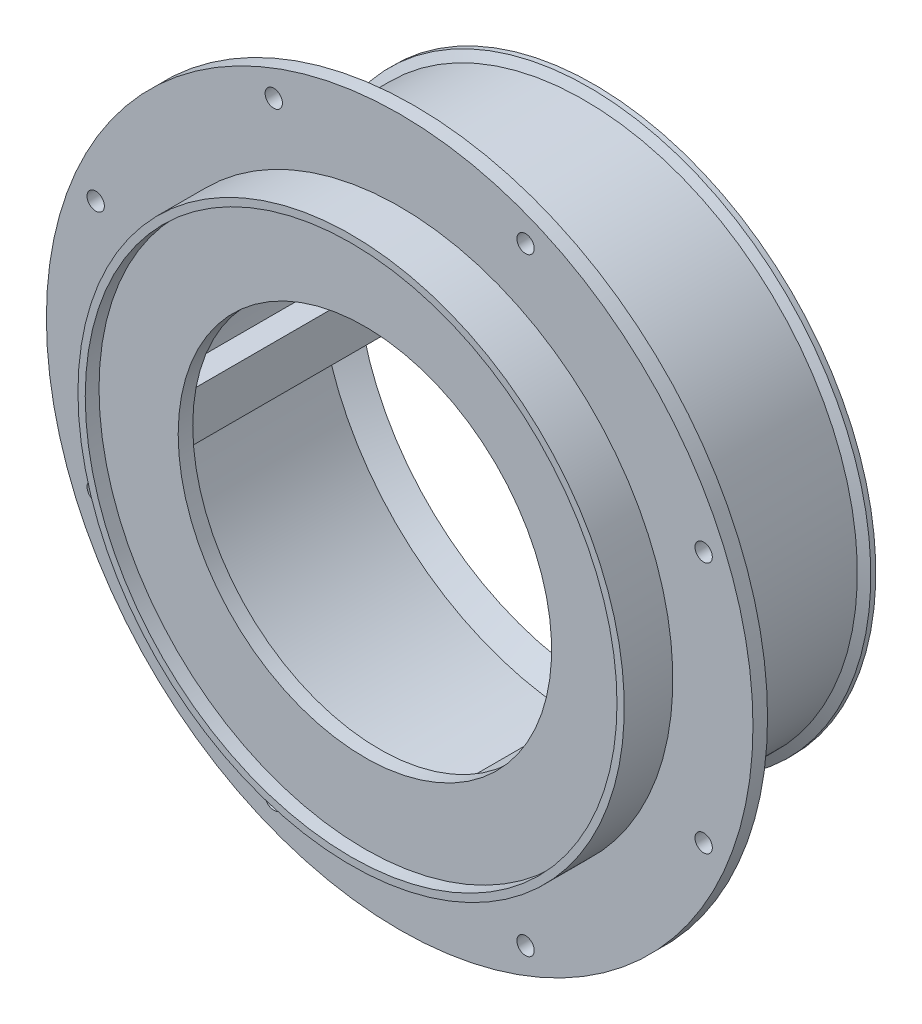
SolidWorks part; units mm, degrees
material "5052-O"
ref_plane "正面" through (0, 0, 0) normal (0, 0, 1) x (1, 0, 0)
ref_plane "平面" through (0, 0, 0) normal (0, 1, 0) x (1, 0, 0)
ref_plane "右側面" through (0, 0, 0) normal (1, 0, 0) x (0, 0, -1)
ref_axis "軸1" through (0, 0, -74.0861) along (0, 0, 1)
sketch "ｽｹｯﾁ1" plane through (0, 0, 0) normal (0, 1, 0) x (1, 0, 0)
  line L0 (111.7327, 39.4914) -> (116.091, 39.4914)
  line L1 (116.091, 39.4914) -> (116.091, 37.4354)
  line L2 (116.091, 37.4354) -> (112.5, 35.4783)
  line L3 (112.5, 35.4783) -> (112.5, -34.5086)
  line L4 (112.5, -34.5086) -> (145.5, -34.5086)
  line L5 (145.5, -34.5086) -> (145.5, -40.5086)
  line L6 (145.5, -40.5086) -> (112.5, -40.5086)
  line L7 (112.5, -40.5086) -> (112.5, -60.5086)
  line L8 (112.5, -60.5086) -> (109.5, -60.5086)
  line L9 (109.5, -60.5086) -> (109.5, -54.8318)
  line L10 (109.5, -54.8318) -> (76.8991, -54.8318)
  line L11 (76.8991, -54.8318) -> (76.8991, -48.8318)
  line L12 (76.8991, -48.8318) -> (109.5, -48.8318)
  line L13 (109.5, -48.8318) -> (109.5, 35.4783)
  line L14 (109.5, 35.4783) -> (101.1927, 42.9989)
  line L15 (101.1927, 42.9989) -> (107.8582, 42.9989)
  line L16 (107.8582, 42.9989) -> (111.7327, 39.4914)
  dimension "D1" = 6
  dimension "D2" = 100
  dimension "D3" = 112.5
  dimension "D4" = 80
  dimension "D5" = 6
  dimension "D6" = 3
  dimension "D7" = 145.5
sketch "ｽｹｯﾁ2" plane through (0, 0, 0) normal (0, 1, 0) x (1, 0, 0)
  line L0 (0, 66.0316) -> (0, -95.0573) construction
revolve "回転1" add sketch "ｽｹｯﾁ1" angle 360 about L0
sketch "ｽｹｯﾁ4" plane through (0, 0, 34.5086) normal (0, 0, -1) x (-1, 0, 0)
  line L0 (0, 0) -> (263.5314, 0) construction
  point P3 (125.1857, 51.8536)
  point P4 (125.1857, -51.8536)
  dimension "D1" = 135.5
  dimension "D2" = 135.5
  dimension "D3" = 22.5
  dimension "D4" = 22.5
hole_wizard "1/4 すきま穴1" positions "3Dｽｹｯﾁ1" profile "ｽｹｯﾁ5" hole size "1/4" standard "Ansi Inch" end condition through all
sketch3d "3Dｽｹｯﾁ1"
  point P0 (-125.1857, 51.8536, 34.5086)
  point P3 (-125.1857, -51.8536, 34.5086)
sketch "ｽｹｯﾁ5" plane through (-125.1857, 51.8536, 34.5086) normal (1, 0, 0) x (0, 1, 0)
  line L0 (0, 0) -> (0, 26)
  line L1 (0, 26) -> (3.5712, 26)
  line L2 (3.5712, 26) -> (3.5712, 0)
  line L5 (3.5712, 0) -> (0, 0)
  line L11 (0, -6.35) -> (0, 107.95) construction
  dimension "通し穴の直径" = 7.1425
  dimension "通し穴の深さ" = 26
pattern_circular "円形ﾊﾟﾀｰﾝ1" count 4 over 360 about axis through (0, 0, -74.0861) along (0, 0, 1) of "1/4 すきま穴1"
sketch "ｽｹｯﾁ6" plane through (0, 0, 48.8318) normal (0, 0, -1) x (-1, 0, 0)
  line L0 (-31.3975, -74.2487) -> (-36.3975, -82.909)
  line L1 (80, -10.0666) -> (90, -10.0666)
  line L2 (80, -10.0666) -> (80, 9.9334)
  line L3 (80, 9.9334) -> (90, 9.9334)
  line L4 (90, -10.0666) -> (90, 9.9334)
  line L5 (80, -10.0666) -> (90, 9.9334) construction
  line L6 (80, 9.9334) -> (90, -10.0666) construction
  line L7 (-48.718, -64.2487) -> (-31.3975, -74.2487)
  line L8 (-53.718, -72.909) -> (-36.3975, -82.909)
  line L9 (-48.718, -64.2487) -> (-53.718, -72.909)
  line L10 (-48.6025, 64.3154) -> (-53.6025, 72.9756)
  line L11 (-31.282, 74.3154) -> (-48.6025, 64.3154)
  line L12 (-36.282, 82.9756) -> (-53.6025, 72.9756)
  line L13 (-31.282, 74.3154) -> (-36.282, 82.9756)
  point P0 (85, -0.0666)
  point P16 (0, 0)
  dimension "D1" = 20
  dimension "D2" = 10
  dimension "D3" = 85
  dimension "D4" = 3
extrude "ﾎﾞｽ - 押し出し1" add sketch "ｽｹｯﾁ6" along normal blind 85
sketch "ｽｹｯﾁ7" plane through (0, 0, -36.1682) normal (0, 0, -1) x (-1, 0, 0)
  line L0 (-11.3975, -39.6077) -> (-36.3975, -82.909)
  line L1 (40, -10.0666) -> (90, -10.0666)
  line L2 (40, -10.0666) -> (40, 9.9334)
  line L3 (40, 9.9334) -> (90, 9.9334)
  line L4 (90, -10.0666) -> (90, 9.9334)
  line L5 (40, -10.0666) -> (90, 9.9334) construction
  line L6 (40, 9.9334) -> (90, -10.0666) construction
  line L7 (-53.718, -72.909) -> (-36.3975, -82.909)
  line L8 (-28.718, -29.6077) -> (-53.718, -72.909)
  line L9 (-28.718, -29.6077) -> (-11.3975, -39.6077)
  line L10 (-28.6025, 29.6743) -> (-53.6025, 72.9756)
  line L11 (-36.282, 82.9756) -> (-53.6025, 72.9756)
  line L12 (-11.282, 39.6743) -> (-36.282, 82.9756)
  line L13 (-11.282, 39.6743) -> (-28.6025, 29.6743)
  point P0 (65, -0.0666)
  point P16 (0, 0)
  dimension "D1" = 50
  dimension "D2" = 20
  dimension "D3" = 3
extrude "ﾎﾞｽ - 押し出し2" add sketch "ｽｹｯﾁ7" along normal blind 5
